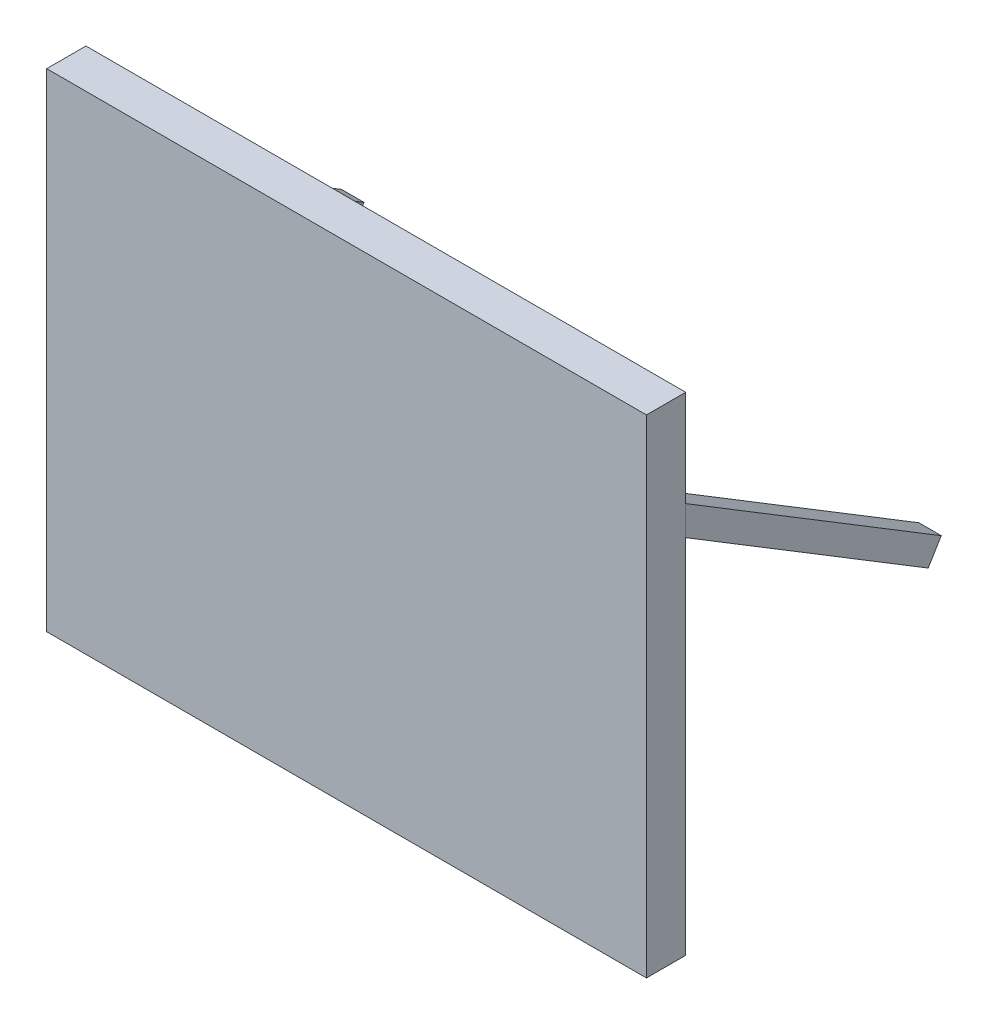
SolidWorks part; units mm, degrees
ref_plane "Front Plane" through (0, 0, 0) normal (0, 0, 1) x (1, 0, 0)
ref_plane "Top Plane" through (0, 0, 0) normal (0, 1, 0) x (1, 0, 0)
ref_plane "Right Plane" through (0, 0, 0) normal (1, 0, 0) x (0, 0, -1)
sketch "Sketch1" plane through (0, 0, 0) normal (0, 0, 1) x (1, 0, 0)
  line L1 (339.725, -276.225) -> (-339.725, -276.225)
  line L2 (339.725, -276.225) -> (339.725, 276.225)
  line L3 (339.725, 276.225) -> (-339.725, 276.225)
  line L4 (-339.725, -276.225) -> (-339.725, 276.225)
  line L5 (339.725, -276.225) -> (-339.725, 276.225) construction
  line L6 (339.725, 276.225) -> (-339.725, -276.225) construction
  point P0 (0, 0)
  point P5 (0, 0)
  dimension "D1" = 679.45
  dimension "D2" = 552.45
extrude "Boss-Extrude1" add sketch "Sketch1" along normal blind 44.45
sketch "Sketch2" plane through (339.725, 0, 0) normal (1, 0, 0) x (0, 0, -1)
  line L0 (0, 166.9952) -> (289.5667, -9.2495)
  line L1 (0, -276.225) -> (0, 276.225) construction
  line L2 (289.5667, -9.2495) -> (274.7201, -33.6422)
  line L3 (274.7201, -33.6422) -> (0, 133.5661)
  line L4 (0, 133.5661) -> (0, 166.9952)
extrude "Boss-Extrude2" add sketch "Sketch2" against normal blind 25.4 separate body
extrude "Boss-Extrude3" add sketch "Sketch2<2>" along normal blind 25.4 from surface starting at face at (-339.725, 0, 22.225)
sketch "Sketch2<2>" plane through (339.725, 0, 0) normal (1, 0, 0) x (0, 0, -1) same geometry as "Sketch2"
